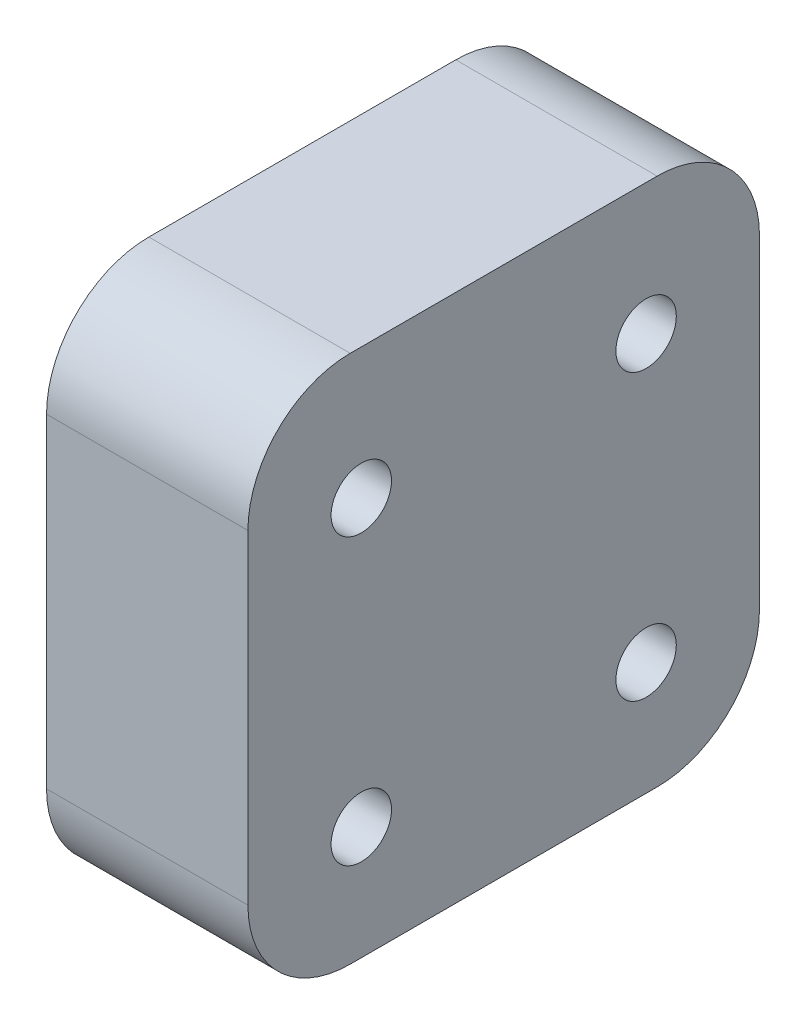
SolidWorks part; units mm, degrees
ref_plane "Front Plane" through (0, 0, 0) normal (0, 0, 1) x (1, 0, 0)
ref_plane "Top Plane" through (0, 0, 0) normal (0, 1, 0) x (1, 0, 0)
ref_plane "Right Plane" through (0, 0, 0) normal (1, 0, 0) x (0, 0, -1)
sketch "Sketch1" plane through (0, 0, 0) normal (0, 1, 0) x (1, 0, 0)
  line L0 (0, 0) -> (10, 0)
  line L1 (10, 0) -> (10, 25.4)
  line L2 (10, 25.4) -> (0, 25.4)
  line L3 (0, 25.4) -> (0, 0)
  dimension "D1" = 10
  dimension "D2" = 25.4
extrude "Boss-Extrude1" add sketch "Sketch1" along normal blind 22.46 and the other way blind 3.81
sketch "Sketch4" plane through (10, 0, 0) normal (1, 0, 0) x (0, 0, -1)
  line L0 (12.7, -3.81) -> (12.7, 8.89)
  line L1 (0, -3.81) -> (25.4, -3.81) construction
  line L2 (12.7, 8.89) -> (19.7711, 1.8189)
  circle A0 centre (19.7711, 1.8189) radius 1.5
  circle A1 centre (5.6289, 1.8189) radius 1.5
  circle A2 centre (5.6289, 15.9611) radius 1.5
  circle A3 centre (19.7711, 15.9611) radius 1.5
  dimension "D4" = 3
  dimension "D1" = 45
  dimension "D2" = 10
  dimension "D3" = 12.7
  dimension "D6" = 14.1421
  dimension "D7" = 10
  dimension "D5" = 4
extrude "Cut-Extrude1" cut sketch "Sketch4" against normal blind 6.35 contours A2 | A3 | A0 | A1 region at (10, 0.4723, -19.2133) region at (10, 1.8189, -5.6289) region at (10, 15.9611, -5.6289) region at (10, 15.9611, -19.7711)
sketch "Sketch5" plane through (10, 0, 0) normal (1, 0, 0) x (0, 0, -1)
  line L0 (19.7711, 15.9611) -> (19.7711, 17.5511)
  line L1 (19.7711, 17.5511) -> (13.3611, 17.5511)
  line L2 (13.3611, 17.5511) -> (13.3611, 0.2311)
  line L3 (13.3611, 0.2311) -> (3.3611, 0.2311)
  line L4 (3.3611, 0.2311) -> (3.3611, 17.5511)
  circle A0 centre (13.3611, 17.5511) radius 1.5
  circle A1 centre (13.3611, 0.2311) radius 1.5
  circle A2 centre (3.3611, 0.2311) radius 1.5
  circle A3 centre (3.3611, 17.5511) radius 1.5
  circle M5 centre (5.6289, 1.8189) radius 1.5
  circle M8 centre (5.6289, 15.9611) radius 1.5
  line M12 (0, 22.46) -> (0, -3.81)
  dimension "D3" = 3
  dimension "D5" = 3
  dimension "D7" = 3
  dimension "D8" = 3
  dimension "D1" = 1.59
  dimension "D2" = 6.41
  dimension "D4" = 17.32
  dimension "D6" = 10
  dimension "D9" = 17.32
extrude "Cut-Extrude2" cut sketch "Sketch5" against normal blind 250 contours A3 M12 M8 | L1 A0 L2 | L2 A0 L1 | L3 A1 L2 | L2 A1 L3 | A2 L4 L3 M5 | L4 A2 L3 M12 | A2 M5 | A3 region at (10, 16.9144, -13.9977) region at (10, 17.7633, -13.1489) region at (10, 17.5716, -3.3317) region at (10, 0.0189, -3.1489) region at (10, 0.8499, -3.9414) region at (10, 0.0189, -13.5733) region at (10, 0.8677, -12.7244) region at (10, 1.025, -4.495)
extrude "Boss-Extrude2" add sketch "Sketch5<3>" against normal blind 6.35 contours A3 M8 | L1 A0 L2 | L2 A0 L1 | L3 A1 L2 | L2 A1 L3 | L4 A2 L3 | L3 A2 L4 M5 region at (10, 16.9144, -13.9977) region at (10, 17.7633, -13.1489) region at (10, 17.5716, -3.3317) region at (10, 0.0189, -3.1489) region at (10, 0.8499, -3.9414) region at (10, 0.0189, -13.5733) region at (10, 0.8677, -12.7244)
sketch "Sketch5<3>" plane through (10, 0, 0) normal (1, 0, 0) x (0, 0, -1) same geometry as "Sketch5"
fillet "Fillet1" radius 5.08 4 edges at (5, 22.46, 0) (5, 22.46, -25.4) (5, -3.81, -25.4) (5, -3.81, 0)
